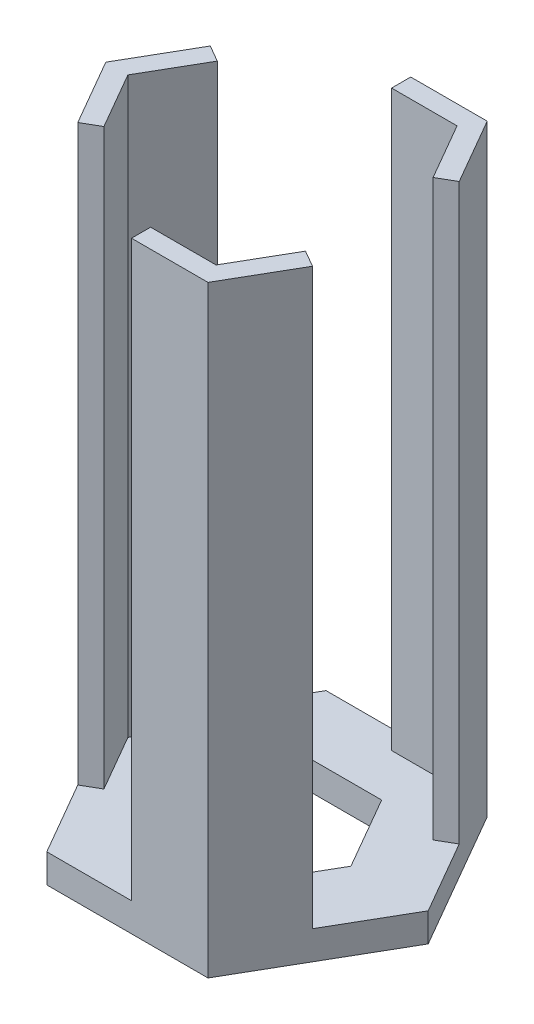
SolidWorks part; units mm, degrees
ref_plane "前视基准面" through (0, 0, 0) normal (0, 0, 1) x (1, 0, 0)
ref_plane "上视基准面" through (0, 0, 0) normal (0, 1, 0) x (1, 0, 0)
ref_plane "右视基准面" through (0, 0, 0) normal (1, 0, 0) x (0, 0, -1)
sketch "草图1" plane through (0, 0, 0) normal (0, 1, 0) x (1, 0, 0)
  line L1 (14.5492, 0) -> (7.2746, 12.6)
  line L2 (7.2746, 12.6) -> (-7.2746, 12.6)
  line L3 (-7.2746, 12.6) -> (-14.5492, 0)
  line L4 (-14.5492, 0) -> (-7.2746, -12.6)
  line L5 (-7.2746, -12.6) -> (7.2746, -12.6)
  line L6 (7.2746, -12.6) -> (14.5492, 0)
  line L7 (-8.7757, 0) -> (-4.3879, -7.6)
  line L8 (-4.3879, -7.6) -> (4.3879, -7.6)
  line L9 (4.3879, -7.6) -> (8.7757, 0)
  line L10 (8.7757, 0) -> (4.3879, 7.6)
  line L11 (4.3879, 7.6) -> (-4.3879, 7.6)
  line L12 (-4.3879, 7.6) -> (-8.7757, 0)
  circle A0 centre (0, 0) radius 12.6 construction
  circle A1 centre (0, 0) radius 7.6 construction
  dimension "D1" = 25.2
  dimension "D2" = 5
extrude "凸台-拉伸1" add sketch "草图1" along normal blind 3
sketch "草图2" plane through (0, 3, 0) normal (0, 1, 0) x (1, 0, 0)
  line L0 (-16.8586, 0) -> (-8.4293, -14.6)
  line L1 (-14.5492, 0) -> (-7.2746, -12.6)
  line L2 (-7.2746, -12.6) -> (7.2746, -12.6)
  line L3 (7.2746, -12.6) -> (14.5492, 0)
  line L4 (14.5492, 0) -> (7.2746, 12.6)
  line L5 (7.2746, 12.6) -> (-7.2746, 12.6)
  line L6 (-7.2746, 12.6) -> (-14.5492, 0)
  line L7 (-8.4293, -14.6) -> (8.4293, -14.6)
  line L8 (8.4293, -14.6) -> (16.8586, 0)
  line L9 (16.8586, 0) -> (8.4293, 14.6)
  line L10 (8.4293, 14.6) -> (-8.4293, 14.6)
  line L11 (-8.4293, 14.6) -> (-16.8586, 0)
  line L12 (-11.1266, 5.9282) -> (-12.8586, 6.9282)
  line L13 (-11.1266, -5.9282) -> (-12.8586, -6.9282)
  line L14 (10.6973, 6.6718) -> (12.4293, 7.6718)
  line L15 (0.4293, 12.6) -> (0.4293, 14.6)
  line L16 (0.4293, -12.6) -> (0.4293, -14.6)
  line L17 (10.6973, -6.6718) -> (12.4293, -7.6718)
  circle A0 centre (0, 0) radius 12.6 construction
  point P29 (0, 0)
  line M1 (7.2746, -12.6) -> (14.5492, 0)
  line M2 (14.5492, 0) -> (7.2746, 12.6)
  line M3 (7.2746, 12.6) -> (-7.2746, 12.6)
  line M4 (-7.2746, 12.6) -> (-14.5492, 0)
  line M5 (-14.5492, 0) -> (-7.2746, -12.6)
  line M6 (-7.2746, -12.6) -> (7.2746, -12.6)
  dimension "D2" = 8
  dimension "D3" = 8
  dimension "D1" = 2
  dimension "D4" = 3
extrude "凸台-拉伸2" add sketch "草图2" along normal blind 60 and the other way up to surface (3 mm away) contours L13 L6 L12 L11 L0 M5 | L15 L4 L14 L9 L10 M3 | L17 L2 L16 L7 L8 M1 region at (-14.7288, 3, -3.3891) region at (0.5731, 3, 13.6) region at (4.4293, 3, -14.4562) other way up to face at (0, 0, 0)
sketch "草图3" plane through (0, 3, 0) normal (0, 1, 0) x (1, 0, 0)
  line L0 (-8.7757, 0) -> (4.3879, -7.6) construction
  line L1 (-4.3879, -7.6) -> (8.7757, 0) construction
  line L2 (4.3879, -7.6) -> (4.3879, 7.6) construction
extrude "凸台-拉伸3" add sketch "草图2<3>" against normal up to surface (3 mm away) contours L5 L15 L10 L11 L12 M4 | L3 L17 L8 L9 L14 M2 | L16 L1 L13 L0 L7 M6 region at (-11.9133, 3, 6.5656) region at (-10.5066, 3, -10.6848) region at (11.646, 3, 7.0286) up to face at (0, 0, 0)
sketch "草图2<3>" plane through (0, 3, 0) normal (0, 1, 0) x (1, 0, 0) same geometry as "草图2"
pattern_linear "阵列(线性)6" [suppressed] count 3 spacing 27.2 along (0.866, 0, 0.5) count 2 spacing 27.2 along (0, 0, 1) of bodies 109
